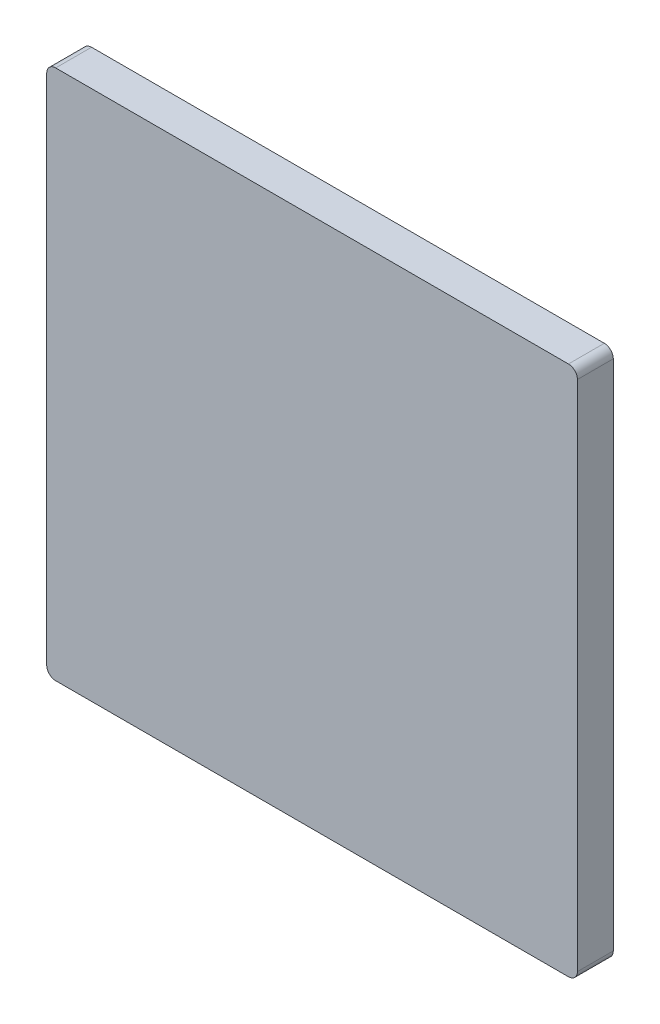
SolidWorks part; units mm, degrees
material "Acrylic (Medium-high impact)"
ref_plane "Front Plane" through (0, 0, 0) normal (0, 0, 1) x (1, 0, 0)
ref_plane "Top Plane" through (0, 0, 0) normal (0, 1, 0) x (1, 0, 0)
ref_plane "Right Plane" through (0, 0, 0) normal (1, 0, 0) x (0, 0, -1)
sketch "Sketch1" plane through (0, 0, 0) normal (0, 0, 1) x (1, 0, 0)
  line L1 (22.7012, -23.495) -> (-22.7012, -23.495)
  line L2 (23.495, -22.7012) -> (23.495, 22.7012)
  line L3 (22.7012, 23.495) -> (-22.7012, 23.495)
  line L4 (-23.495, -22.7012) -> (-23.495, 22.7012)
  line L5 (23.495, -23.495) -> (-23.495, 23.495) construction
  line L6 (23.495, 23.495) -> (-23.495, -23.495) construction
  arc A1 (-23.495, 22.7012) -> (-22.7012, 23.495) centre (-22.7013, 22.7012) cw
  arc A2 (22.7012, 23.495) -> (23.495, 22.7012) centre (22.7012, 22.7013) cw
  arc A3 (23.495, -22.7012) -> (22.7012, -23.495) centre (22.7012, -22.7012) cw
  arc A4 (-22.7012, -23.495) -> (-23.495, -22.7012) centre (-22.7013, -22.7013) cw
  dimension "D1" = 0.7937
  dimension "D2" = 46.99
  dimension "D3" = 46.99
extrude "Boss-Extrude1" add sketch "Sketch1" along normal blind 3.175
